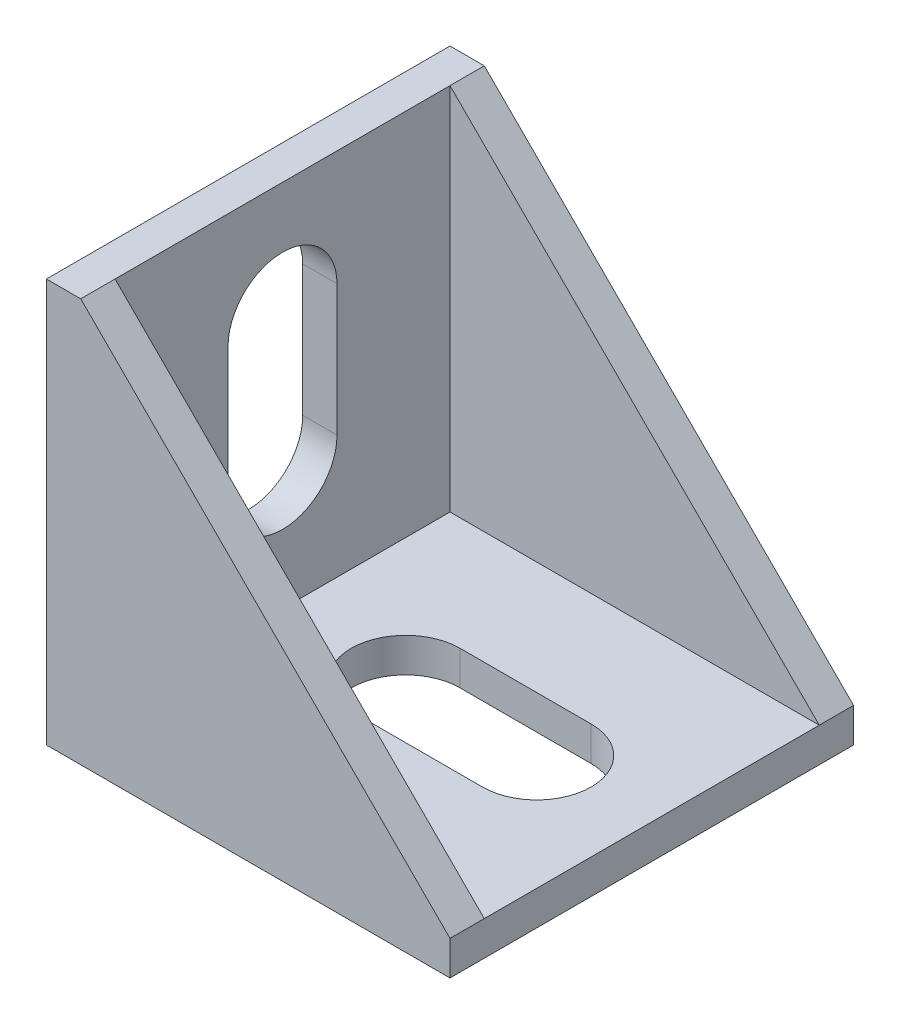
SolidWorks part; units mm, degrees
material "1060-H18"
ref_plane "Přední rovina" through (0, 0, 0) normal (0, 0, 1) x (1, 0, 0)
ref_plane "Horní rovina" through (0, 0, 0) normal (0, 1, 0) x (1, 0, 0)
ref_plane "Pravá rovina" through (0, 0, 0) normal (1, 0, 0) x (0, 0, -1)
sketch "Skica1" plane through (0, 0, 0) normal (0, 1, 0) x (1, 0, 0)
  line L0 (-2.2, 0) -> (4.3, 0) construction
  line L1 (-10, -10) -> (10, -10)
  line L2 (-10, -10) -> (-10, 10)
  line L3 (-10, 10) -> (10, 10)
  line L4 (10, -10) -> (10, 10)
  line L5 (-10, -10) -> (10, 10) construction
  line L6 (-10, 10) -> (10, -10) construction
  line L7 (-2.2, 2.7) -> (4.3, 2.7)
  line L8 (-2.2, -2.7) -> (4.3, -2.7)
  arc A0 (-2.2, 2.7) -> (-2.2, -2.7) centre (-2.2, 0) ccw
  arc A1 (4.3, -2.7) -> (4.3, 2.7) centre (4.3, 0) ccw
  point P0 (0, 0)
  point P8 (1.05, 0)
  dimension "D1" = 20
  dimension "D2" = 20
  dimension "D3" = 6.5
  dimension "D4" = 5.4
  dimension "D5" = 5.7
extrude "Přidat vysunutím1" add sketch "Skica1" along normal blind 1.7
sketch "Skica2" plane through (0, 1.7, 0) normal (0, 1, 0) x (1, 0, 0)
  line L0 (-10, -10) -> (10, -10) construction
  line L1 (-10, 10) -> (-8.3, 10)
  line L2 (-10, 10) -> (-10, -10)
  line L3 (-10, -10) -> (-8.3, -10)
  line L4 (-8.3, 10) -> (-8.3, -10)
  line L5 (-10, 10) -> (-8.3, -10) construction
  line L6 (-10, -10) -> (-8.3, 10) construction
  point P4 (-9.15, 0)
  dimension "D1" = 1.7
extrude "Přidat vysunutím2" add sketch "Skica2" along normal blind 18.3
sketch "Skica3" plane through (-8.3, 0, 0) normal (1, 0, 0) x (0, 0, -1)
  line L0 (0, 14.3) -> (0, 7.8) construction
  line L1 (2.7, 14.3) -> (2.7, 7.8)
  line L2 (-2.7, 14.3) -> (-2.7, 7.8)
  line L3 (-10, 20) -> (10, 20) construction
  arc A0 (2.7, 14.3) -> (-2.7, 14.3) centre (0, 14.3) ccw
  arc A1 (-2.7, 7.8) -> (2.7, 7.8) centre (0, 7.8) ccw
  point P3 (0, 11.05)
  point P10 (0, 20)
  dimension "D1" = 5.7
  dimension "D2" = 6.5
  dimension "D3" = 5.4
extrude "Odebrat vysunutím1" cut sketch "Skica3" against normal up to surface (1.7 mm away) up to face at (-10, 10, 0)
sketch "Skica4" plane through (-8.3, 0, 0) normal (1, 0, 0) x (0, 0, -1)
  line L0 (-10, 1.7) -> (10, 1.7) construction
  line L1 (-10, 20) -> (-8.3, 20)
  line L2 (-10, 20) -> (-10, 1.7)
  line L3 (-10, 1.7) -> (-8.3, 1.7)
  line L4 (-8.3, 20) -> (-8.3, 1.7)
  line L5 (-10, 20) -> (-8.3, 1.7) construction
  line L6 (-10, 1.7) -> (-8.3, 20) construction
  line L7 (0, 20) -> (0, 1.7) construction
  line L8 (-10, 20) -> (10, 20) construction
  line L9 (10, 1.7) -> (8.3, 1.7)
  line L10 (10, 20) -> (10, 1.7)
  line L11 (10, 20) -> (8.3, 20)
  line L12 (8.3, 20) -> (8.3, 1.7)
  point P4 (-9.15, 10.85)
  dimension "D1" = 1.7
extrude "Přidat vysunutím3" add sketch "Skica4" along normal blind 18.3
chamfer "Zkosení1" distance 18.3 angle 45 2 edges at (10, 20, -9.15) (10, 20, 9.15)
